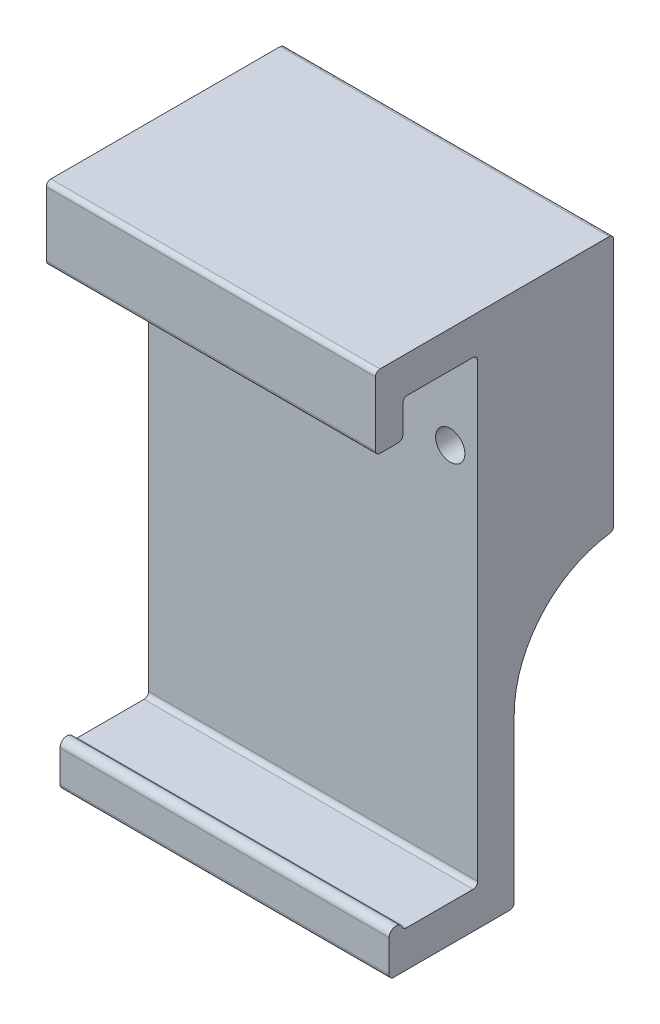
SolidWorks part; units mm, degrees
ref_plane "Front Plane" through (0, 0, 0) normal (0, 0, 1) x (1, 0, 0)
ref_plane "Top Plane" through (0, 0, 0) normal (0, 1, 0) x (1, 0, 0)
ref_plane "Right Plane" through (0, 0, 0) normal (1, 0, 0) x (0, 0, -1)
sketch "Sketch2" plane through (0, 0, 0) normal (1, 0, 0) x (0, 0, -1)
  line L0 (-3.25, 16.825) -> (-5.6312, 16.825)
  line L1 (-3.25, -20) -> (3.25, -20) construction
  line L2 (-3.25, -20) -> (-3.25, 20) construction
  line L3 (-3.25, 20) -> (3.25, 20) construction
  line L4 (3.25, -20) -> (3.25, 20) construction
  line L5 (-3.25, -20) -> (3.25, 20) construction
  line L6 (-3.25, 20) -> (3.25, -20) construction
  line L7 (-5.6312, 16.825) -> (-5.6312, 23.175)
  line L8 (-5.6312, 23.175) -> (6.425, 23.175)
  line L9 (6.425, 23.175) -> (6.425, -23.175)
  line L10 (6.425, -23.175) -> (-4.4406, -23.175)
  line L11 (-4.4406, -23.175) -> (-4.4406, -20)
  line L12 (-3.25, 16.825) -> (-3.25, 20)
  line L13 (-3.25, 20) -> (3.25, 20)
  line L14 (3.25, 20) -> (3.25, -20)
  line L15 (3.25, -20) -> (-3.25, -20)
  line L16 (-4.4406, -20) -> (-3.25, -20) construction
  line L17 (-5.6312, 23.175) -> (-3.25, 20) construction
  line L18 (3.25, 20) -> (6.425, 23.175) construction
  line L19 (3.25, -20) -> (6.425, -23.175) construction
  arc A0 (-3.25, -20) -> (-4.4406, -20) centre (-3.8453, -20) ccw
  point P0 (0, 0)
  point P13 (-5.8255, 22.5755)
  point P15 (-3.25, 16.611)
  point P16 (11.8377, 23.175)
  point P17 (-5.2029, 16.9928)
  point P18 (-4.4406, -20)
  point P19 (-4.409, -23.175)
  dimension "D3" = 0.5953
  dimension "D1" = 40
  dimension "D2" = 6.5
  dimension "D4" = 3.175
  dimension "D5" = 2.3813
  dimension "D6" = 3.175
extrude "Boss-Extrude1" add sketch "Sketch2" along normal mid plane 28.575
fillet "Fillet1" radius 0.3969 8 edges at (0, 16.825, 3.25) (0, 16.825, 5.6312) (0, 23.175, 5.6312) (0, -23.175, 4.4406) (0, 20, -3.25) (0, 20, 3.25) (0, -20, -3.25) (0, -20, 3.25)
sketch "Sketch3" plane through (0, 0, 0) normal (1, 0, 0) x (0, 0, -1)
  line L0 (6.425, -23.175) -> (6.425, 23.175) construction
  line L1 (6.425, 23.175) -> (15.061, 23.175)
  line L2 (15.061, 23.175) -> (15.061, 20.635)
  line L3 (15.061, 3.363) -> (15.061, 0.823)
  line L4 (15.061, 0.823) -> (6.425, 0.823)
  line L5 (15.061, 20.635) -> (15.061, 3.363)
  line L6 (6.425, 23.175) -> (6.425, 0.823)
  circle A0 centre (15.061, 11.999) radius 8.636 construction
  point P10 (15.061, -5.7727)
  dimension "D1" = 17.272
  dimension "D2" = 2.54
extrude "Boss-Extrude2" add sketch "Sketch3" along normal mid plane 28.575
sketch "Sketch4" plane through (0, 0, 0) normal (1, 0, 0) x (0, 0, -1)
  line L0 (15.061, 3.363) -> (15.061, 20.635)
  circle A0 centre (15.061, 11.999) radius 8.636 construction
  circle A1 centre (15.061, 11.999) radius 8.636 construction
  arc A2 (15.061, 20.635) -> (15.061, 3.363) centre (15.061, 11.999) ccw
ref_axis "Axis1" through (0, 11.999, -15.061) along (0, 1, 0)
revolve "Cut-Revolve3" cut sketch "Sketch4" angle 360 about L0
fillet "Fillet2" radius 0.3969 4 edges at (0, 3.363, -15.061) (0, 23.175, -15.061) (0, 0.823, -15.061) (0, -23.175, -6.425)
sketch "Sketch5" plane through (0, 0, -15.061) normal (0, 0, -1) x (-1, 0, 0)
  line L0 (11.9062, 11.999) -> (-11.9062, 11.999) construction
  line L1 (0, 11.999) -> (0, 81.0447) construction
  circle A0 centre (0, 11.999) radius 8.6277 construction
  circle A1 centre (-11.9062, 11.999) radius 1.27
  circle A2 centre (11.9062, 11.999) radius 1.27
  point P2 (0, 11.999)
  point P7 (-8.6218, 4.9882)
  dimension "D2" = 2.54
  dimension "D1" = 23.8125
  dimension "D3" = 90
extrude "Cut-Extrude1" cut sketch "Sketch5" against normal blind 12.7
fillet "Fillet3" radius 9.525 1 edges at (0, 0.823, -6.425)
